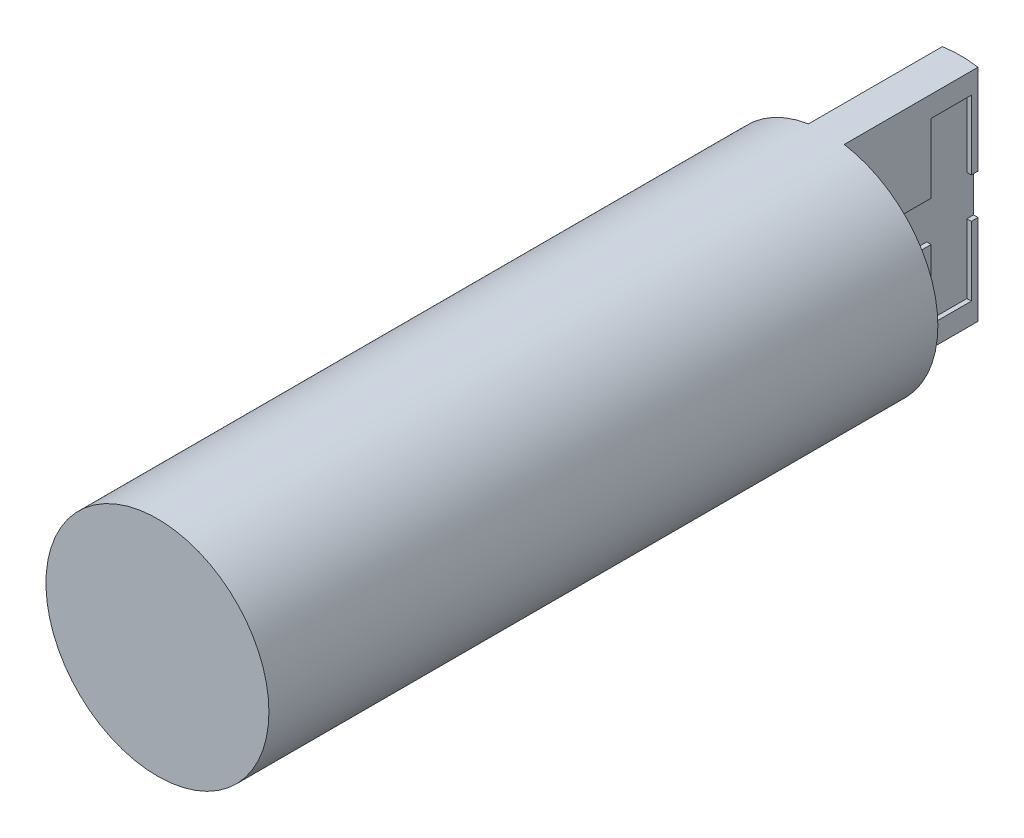
SolidWorks part; units mm, degrees
ref_plane "Plan de face" through (0, 0, 0) normal (0, 0, 1) x (1, 0, 0)
ref_plane "Plan de dessus" through (0, 0, 0) normal (0, 1, 0) x (1, 0, 0)
ref_plane "Plan de droite" through (0, 0, 0) normal (1, 0, 0) x (0, 0, -1)
sketch "Esquisse1" plane through (0, 0, 0) normal (0, 0, 1) x (1, 0, 0)
  circle A0 centre (0, 0) radius 25
  dimension "D1" = 50
extrude "Boss.-Extru.1" add sketch "Esquisse1" along normal blind 150
sketch "Esquisse2" plane through (0, 0, 0) normal (0, 0, -1) x (-1, 0, 0)
  line L0 (0, 0) -> (0, 38.1422) construction
  line L1 (0, 0) -> (59.9191, 0) construction
  line L4 (-4, -24.6779) -> (-4, 24.6779)
  line L6 (4, -24.6779) -> (4, 24.6779)
  line L7 (-4, -24.6779) -> (4, 24.6779) construction
  line L8 (-4, 24.6779) -> (4, -24.6779) construction
  circle A0 centre (0, 0) radius 25 construction
  arc A1 (4, 24.6779) -> (-4, 24.6779) centre (0, 0) ccw
  arc A2 (-4, -24.6779) -> (4, -24.6779) centre (0, 0) ccw
  dimension "D1" = 8
extrude "Boss.-Extru.2" add sketch "Esquisse2" along normal blind 30
sketch "Esquisse3" plane through (-4, 0, 0) normal (-1, 0, 0) x (0, 0, 1)
  line L0 (0, 0) -> (-30, 0) construction
  line L1 (0, -24.6779) -> (0, 24.6779) construction
  line L2 (-30, -24.6779) -> (-30, 24.6779) construction
  circle A0 centre (-24, 0) radius 6
  dimension "D1" = 12
extrude "Boss.-Extru.3" add sketch "Esquisse3" along normal blind 9 draft 1 contours A0
sketch "Esquisse4" plane through (4, 0, 0) normal (1, 0, 0) x (0, 0, -1)
  line L0 (0, 0) -> (30, 0) construction
  line L1 (0, 24.6779) -> (0, -24.6779) construction
  line L2 (30, 24.6779) -> (30, -24.6779) construction
  line L3 (19.5, 4.5) -> (19.5, 20)
  line L4 (4, 4.5) -> (19.5, 4.5)
  line L5 (4, 4.5) -> (4, -4.5)
  line L6 (4, -4.5) -> (19.5, -4.5)
  line L8 (4, 4.5) -> (24, -4.5) construction
  line L9 (4, -4.5) -> (24, 4.5) construction
  line L10 (28.5, -20) -> (19.5, -20)
  line L11 (28.5, -20) -> (28.5, -4.5)
  line L12 (28.5, 20) -> (19.5, 20)
  line L13 (19.5, -20) -> (19.5, -4.5)
  line L14 (28.5, -20) -> (19.5, 20) construction
  line L15 (28.5, 20) -> (19.5, -20) construction
  line L16 (28.5, -4.5) -> (30, -4.5)
  line L17 (28.5, 4.5) -> (30, 4.5)
  line L20 (30, 4.5) -> (30, -4.5)
  line L21 (28.5, 4.5) -> (28.5, 20)
  circle A0 centre (24, 0) radius 6 construction
  circle A1 centre (24, 0) radius 6 construction
  circle A2 centre (24, 0) radius 4.5 construction
  point P10 (14, 0)
  dimension "D1" = 9
  dimension "D3" = 40
extrude "Enlèv. mat.-Extru.1" cut sketch "Esquisse4" against normal blind 1
ref_axis "Axe1" through (0, 0, -39) along (0, 0, 1)
